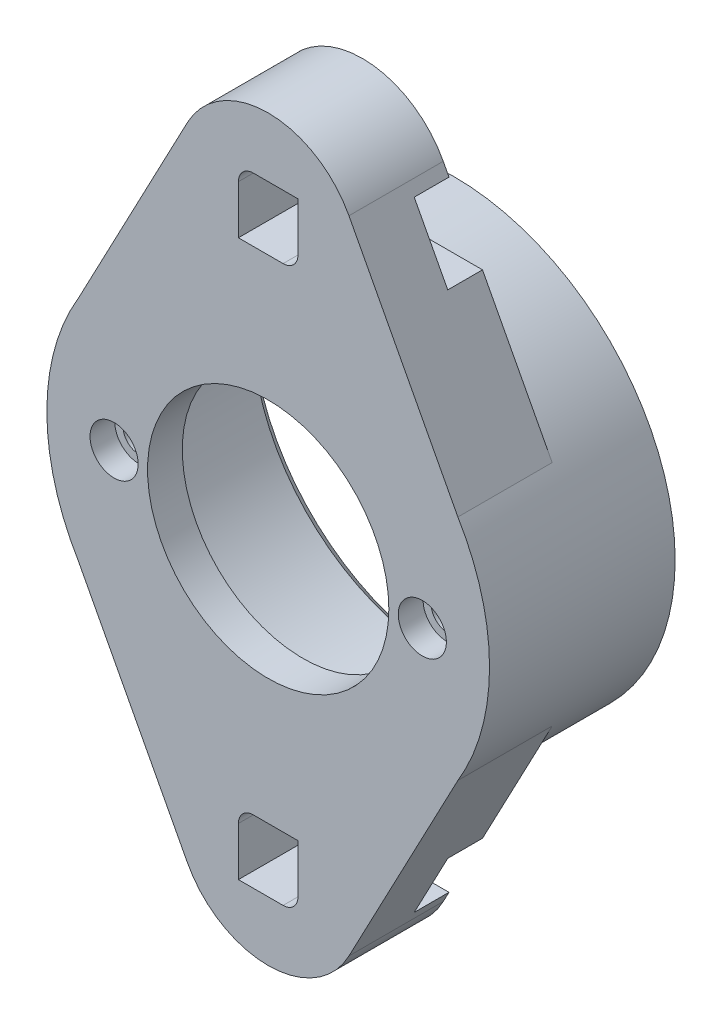
SolidWorks part; units mm, degrees
ref_plane "Front" through (0, 0, 0) normal (0, 0, 1) x (1, 0, 0)
ref_plane "Top" through (0, 0, 0) normal (0, 1, 0) x (1, 0, 0)
ref_plane "Right" through (0, 0, 0) normal (1, 0, 0) x (0, 0, -1)
sketch "Sketch1" plane through (0, 0, 0) normal (0, 0, 1) x (1, 0, 0)
  circle A2 centre (0, 0) radius 19.1 construction
  circle A3 centre (0, 0) radius 22.3
  circle A5 centre (0, 0) radius 12.155
  circle A6 centre (0, 0) radius 19.3
  circle A14 centre (-15.5275, 0) radius 1.6
  circle A17 centre (15.5275, 0) radius 1.6
  dimension "D5" = 0.2
  dimension "D6" = 3
extrude "Boss-Extrude1" add sketch "Sketch1" along normal blind 1 contours A6 A17 A14 A5 | A3 A6 region at (-21.6693, 0, 0) region at (-18.7541, 0, 0)
extrude "Boss-Extrude2" add sketch "Sketch1<3>" against normal blind 15.2 contours A3 A6 region at (-21.6693, 0, 0)
sketch "Sketch1<3>" plane through (0, 0, 0) normal (0, 0, 1) x (1, 0, 0) same geometry as "Sketch1"
sketch "Sketch3" plane through (0, 0, 1) normal (0, 0, 1) x (1, 0, 0)
  circle A0 centre (-15.5275, 0) radius 2.225 construction
  circle A1 centre (15.5275, 0) radius 2.225 construction
  circle A2 centre (-15.5275, 0) radius 2.425
  circle A3 centre (15.5275, 0) radius 2.425
  circle A4 centre (0, 0) radius 12.155 construction
  circle A5 centre (0, 0) radius 22.3
  circle A6 centre (0, 0) radius 22.3
  circle A7 centre (0, 0) radius 12.155
  dimension "D1" = 4.45
  dimension "D2" = 0.2
  dimension "D3" = 0
extrude "Boss-Extrude3" add sketch "Sketch3" along normal blind 2.5
sketch "Sketch4" plane through (0, 0, 3.5) normal (0, 0, 1) x (1, 0, 0)
  line L0 (0, 28) -> (0, -28) construction
  line L1 (-20.2747, -9.2859) -> (-8.1371, -32.2928)
  line L2 (20.2747, -9.2859) -> (8.1371, -32.2928)
  line L3 (0, 0) -> (10.274, 0) construction
  line L4 (-20.2747, -9.2859) -> (-8.1371, -32.2928)
  line L5 (20.2747, -9.2859) -> (8.1371, -32.2928)
  line L6 (-20.2747, -9.2859) -> (-8.1371, -32.2928)
  line L7 (20.2747, -9.2859) -> (8.1371, -32.2928)
  line L8 (-20.2747, -9.2859) -> (-8.1371, -32.2928)
  line L9 (20.2747, -9.2859) -> (8.1371, -32.2928)
  line L10 (20.2747, 9.2859) -> (8.1371, 32.2928)
  line L11 (-20.2747, 9.2859) -> (-8.1371, 32.2928)
  line L12 (20.2747, 9.2859) -> (8.1371, 32.2928)
  line L13 (-20.2747, 9.2859) -> (-8.1371, 32.2928)
  line L14 (20.2747, 9.2859) -> (8.1371, 32.2928)
  line L15 (-20.2747, 9.2859) -> (-8.1371, 32.2928)
  line L16 (20.2747, 9.2859) -> (8.1371, 32.2928)
  line L17 (-20.2747, 9.2859) -> (-8.1371, 32.2928)
  line L18 (-2.8, -28) -> (2.8, -28)
  line L19 (3, -24.8) -> (-3, -24.8)
  line L20 (2.8, -31) -> (-2.8, -31) construction
  line L21 (2.8, -31) -> (2.8, -25) construction
  line L22 (2.8, -25) -> (-2.8, -25) construction
  line L23 (-2.8, -31) -> (-2.8, -25) construction
  line L24 (2.8, -31) -> (-2.8, -25) construction
  line L25 (2.8, -25) -> (-2.8, -31) construction
  line L26 (-3, -31.2) -> (-3, -24.8)
  line L27 (3, -31.2) -> (-3, -31.2)
  line L28 (3, -31.2) -> (3, -24.8)
  line L29 (3, 31.2) -> (-3, 31.2)
  line L30 (3, 31.2) -> (3, 24.8)
  line L31 (3, 24.8) -> (-3, 24.8)
  line L32 (-3, 31.2) -> (-3, 24.8)
  arc A2 (-8.1371, -32.2928) -> (8.1371, -32.2928) centre (0, -28) ccw
  arc A3 (8.1371, -32.2928) -> (-8.1371, -32.2928) centre (0, -28) ccw construction
  circle A4 centre (0, 0) radius 22.3 construction
  circle A5 centre (0, 0) radius 22.3
  arc A7 (8.1371, -32.2928) -> (-8.1371, -32.2928) centre (0, -28) ccw construction
  arc A8 (8.1371, 32.2928) -> (-8.1371, 32.2928) centre (0, 28) cw construction
  arc A9 (8.1371, 32.2928) -> (-8.1371, 32.2928) centre (0, 28) cw construction
  arc A11 (-8.1371, 32.2928) -> (8.1371, 32.2928) centre (0, 28) cw
  point P28 (0, -28)
  circle M2 centre (0, 0) radius 22.3
  dimension "D1" = 6
  dimension "D4" = 28
  dimension "D5" = 5.6
  dimension "D2" = 0.2
extrude "Boss-Extrude4" add sketch "Sketch4" against normal blind 6 contours A11 L11 L10 M2 | L1 A2 L2 M2 region at (0, -22.7606, 3.5) region at (-13.2164, 21.6777, 3.5)
chamfer "Chamfer1" distance 1 angle 45 1 edges at (19.3, 0, -15.2)
sketch "Sketch5" plane through (0, 0, -2.5) normal (0, 0, -1) x (-1, 0, 0)
  line L0 (0, 0) -> (-39.5514, 0) construction
  line L5 (-16.4788, -31.2) -> (16.4788, -31.2)
  line L6 (-16.4788, -31.2) -> (-16.4788, -24.8)
  line L7 (-16.4788, -24.8) -> (16.4788, -24.8)
  line L8 (16.4788, -31.2) -> (16.4788, -24.8)
  line L9 (-3, -24.8) -> (3, -24.8) construction
  line L10 (-3, -31.2) -> (3, -31.2) construction
  line L11 (-16.4788, 24.8) -> (16.4788, 31.2) construction
  line L12 (8.1371, -32.2928) -> (19.1106, -11.4924)
  line L13 (-19.1106, -11.4924) -> (-8.1371, -32.2928)
  line L14 (8.1371, -32.2928) -> (19.1106, -11.4924)
  line L15 (-19.1106, -11.4924) -> (-8.1371, -32.2928)
  line L16 (-8.1371, 32.2928) -> (-19.1106, 11.4924)
  line L17 (19.1106, 11.4924) -> (8.1371, 32.2928)
  line L18 (-8.1371, 32.2928) -> (-19.1106, 11.4924)
  line L19 (19.1106, 11.4924) -> (8.1371, 32.2928)
  line L20 (-16.4788, 31.2) -> (16.4788, 24.8) construction
  line L21 (-19.1106, 11.4924) -> (-8.1371, 32.2928)
  line L22 (8.1371, 32.2928) -> (19.1106, 11.4924)
  line L23 (16.4788, 31.2) -> (16.4788, 24.8)
  line L24 (-16.4788, 24.8) -> (16.4788, 24.8)
  line L25 (-16.4788, 31.2) -> (-16.4788, 24.8)
  line L26 (-16.4788, 31.2) -> (16.4788, 31.2)
  arc A6 (-19.1106, -11.4924) -> (19.1106, -11.4924) centre (0, 0) ccw
  arc A7 (-8.1371, -32.2928) -> (8.1371, -32.2928) centre (0, -28) ccw
  arc A8 (-19.1106, -11.4924) -> (19.1106, -11.4924) centre (0, 0) ccw
  arc A9 (-8.1371, -32.2928) -> (8.1371, -32.2928) centre (0, -28) ccw
  arc A10 (8.1371, 32.2928) -> (-8.1371, 32.2928) centre (0, 28) ccw
  arc A11 (19.1106, 11.4924) -> (-19.1106, 11.4924) centre (0, 0) ccw
  arc A12 (8.1371, 32.2928) -> (-8.1371, 32.2928) centre (0, 28) ccw
  arc A13 (19.1106, 11.4924) -> (-19.1106, 11.4924) centre (0, 0) ccw
  arc A14 (-8.1371, 32.2928) -> (8.1371, 32.2928) centre (0, 28) cw
  arc M1 (8.1371, 32.2928) -> (-8.1371, 32.2928) centre (0, 28) ccw
  line M2 (-8.1371, 32.2928) -> (-19.1106, 11.4924)
  arc M3 (-19.1106, 11.4924) -> (19.1106, 11.4924) centre (0, 0) cw
  line M4 (19.1106, 11.4924) -> (8.1371, 32.2928)
  dimension "D1" = 0
  dimension "D2" = 0
extrude "Boss-Extrude5" add sketch "Sketch5" along normal blind 3.5 contours L24 L21 M3 M4 | L26 M2 M4 M1 | A8 L15 L7 L14 | L15 A9 L14 L5 region at (0, -33.6811, -2.5) region at (15.2423, -17.9573, -2.5) region at (0, 33.6811, -2.5) region at (0, 24.3953, -2.5)
fillet "Fillet1" radius 1.5 4 edges at (3, -31.2, 0.5) (-3, -24.8, 0.5) (3, 24.8, 0.5) (-3, 31.2, 0.5)
